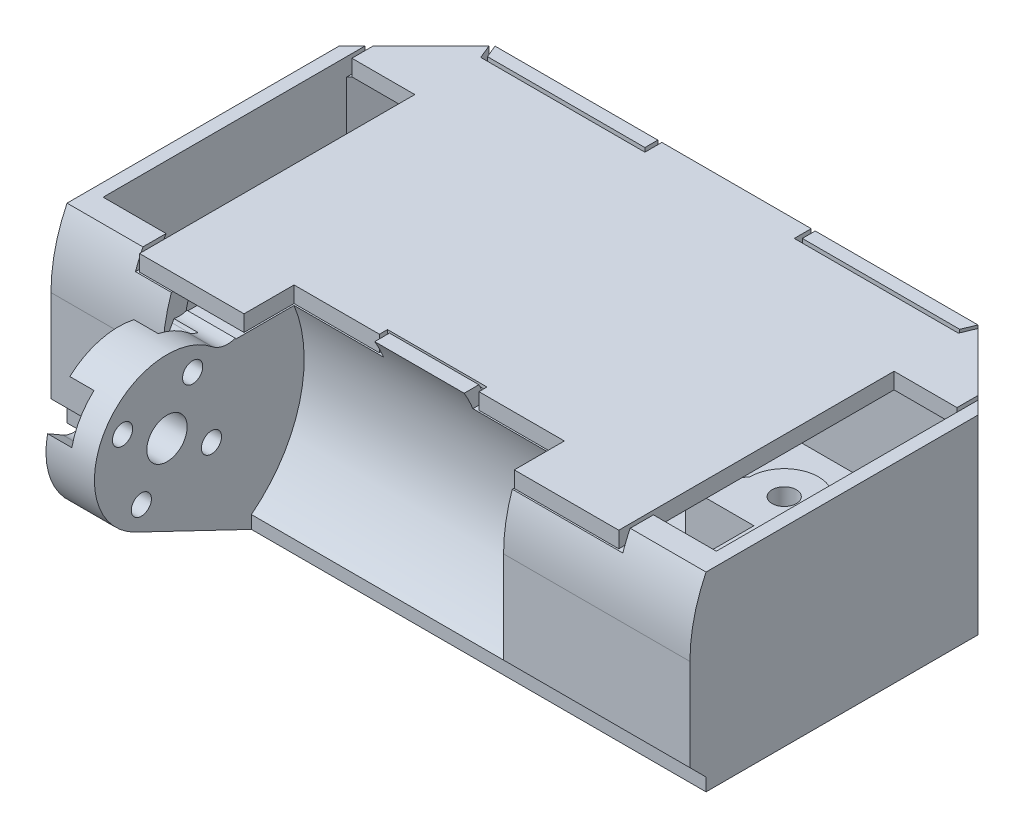
SolidWorks part; units mm, degrees
material "ABS PC"
ref_plane "Front Plane" through (0, 0, 0) normal (0, 0, 1) x (1, 0, 0)
ref_plane "Top Plane" through (0, 0, 0) normal (0, 1, 0) x (1, 0, 0)
ref_plane "Right Plane" through (0, 0, 0) normal (1, 0, 0) x (0, 0, -1)
sketch "Sketch1" plane through (0, 0, 0) normal (0, 1, 0) x (1, 0, 0)
  line L0 (0, -309.2525) -> (0, 15153.3717) construction
  line L1 (28.2, 1.5) -> (28.2, -1.5) construction
  line L2 (3, -6) -> (27, -6)
  line L3 (3, -6) -> (3, 6)
  line L4 (3, 6) -> (27, 6)
  line L5 (27, -6) -> (27, 6)
  line L6 (15, 6) -> (15, -6) construction
  line L7 (3, 0) -> (27, 0) construction
  line L8 (27.7, -2) -> (27, -2)
  line L9 (27.7, -2) -> (27.7, 2)
  line L10 (27.7, 2) -> (27, 2)
  line L11 (27, -2) -> (27, 2)
  line L12 (27.35, 2) -> (27.35, -2) construction
  line L13 (27.7, 0) -> (27, 0) construction
  line L14 (37, -1.5) -> (27.7, -1.5)
  line L15 (37, -1.5) -> (37, 1.5)
  line L16 (37, 1.5) -> (27.7, 1.5)
  line L17 (27.7, -1.5) -> (27.7, 1.5)
  line L18 (32.35, 1.5) -> (32.35, -1.5) construction
  line L19 (37, 0) -> (27.7, 0) construction
  line L20 (36.8, -16) -> (30.2, -16)
  line L21 (36.8, -16) -> (36.8, 16)
  line L22 (36.8, 16) -> (30.2, 16)
  line L23 (30.2, -16) -> (30.2, 16)
  line L24 (33.5, 16) -> (33.5, -16) construction
  line L25 (36.8, 0) -> (30.2, 0) construction
  line L26 (27, -7.5) -> (15.5, -7.5)
  line L27 (27, -7.5) -> (27, 7.5)
  line L28 (27, 7.5) -> (15.5, 7.5)
  line L29 (15.5, -7.5) -> (15.5, 7.5)
  line L30 (21.25, 7.5) -> (21.25, -7.5) construction
  line L31 (27, 0) -> (3, 0) construction
  line L32 (-27, 0) -> (-3, 0) construction
  line L33 (-21.25, 7.5) -> (-21.25, -7.5) construction
  line L34 (-36.8, 0) -> (-30.2, 0) construction
  line L35 (-33.5, 16) -> (-33.5, -16) construction
  line L36 (-37, 0) -> (-27.7, 0) construction
  line L37 (-32.35, 1.5) -> (-32.35, -1.5) construction
  line L38 (-27.7, 0) -> (-27, 0) construction
  line L39 (-27.35, 2) -> (-27.35, -2) construction
  line L40 (-3, 0) -> (-27, 0) construction
  line L41 (-15, 6) -> (-15, -6) construction
  line L42 (-28.2, 1.5) -> (-28.2, -1.5) construction
  line L43 (-15.5, -7.5) -> (-15.5, 7.5)
  line L44 (-27, 7.5) -> (-15.5, 7.5)
  line L45 (-27, -7.5) -> (-27, 7.5)
  line L46 (-27, -7.5) -> (-15.5, -7.5)
  line L47 (-30.2, -16) -> (-30.2, 16)
  line L48 (-36.8, 16) -> (-30.2, 16)
  line L49 (-36.8, -16) -> (-36.8, 16)
  line L50 (-36.8, -16) -> (-30.2, -16)
  line L51 (-27.7, -1.5) -> (-27.7, 1.5)
  line L52 (-37, 1.5) -> (-27.7, 1.5)
  line L53 (-37, -1.5) -> (-37, 1.5)
  line L54 (-37, -1.5) -> (-27.7, -1.5)
  line L55 (-27, -2) -> (-27, 2)
  line L56 (-27.7, 2) -> (-27, 2)
  line L57 (-27.7, -2) -> (-27.7, 2)
  line L58 (-27.7, -2) -> (-27, -2)
  line L59 (-27, -6) -> (-27, 6)
  line L60 (-3, 6) -> (-27, 6)
  line L61 (-3, -6) -> (-3, 6)
  line L62 (-3, -6) -> (-27, -6)
  line L63 (38, -995.0782) -> (38, 49004.9218) construction
  line L64 (-38, -995.0782) -> (-38, 49004.9218) construction
  line L65 (22.75, -9) -> (22.75, 9) construction
  line L66 (18.5, -9) -> (18.5, 9)
  line L67 (27, -9) -> (27, 9)
  line L68 (-22.75, -9) -> (-22.75, 9) construction
  line L69 (-18.5, -9) -> (-18.5, 9)
  line L70 (-27, -9) -> (-27, 9)
  circle A0 centre (22.75, 9) radius 1.5
  circle A1 centre (22.75, -9) radius 1.5
  circle A2 centre (-22.75, -9) radius 1.5
  circle A3 centre (-22.75, 9) radius 1.5
  arc A4 (18.5, -9) -> (27, -9) centre (22.75, -9) ccw
  arc A5 (27, 9) -> (18.5, 9) centre (22.75, 9) ccw
  arc A6 (-18.5, -9) -> (-27, -9) centre (-22.75, -9) cw
  arc A7 (-27, 9) -> (-18.5, 9) centre (-22.75, 9) cw
  point P1 (15, 0)
  point P7 (27.35, 0)
  point P12 (32.35, 0)
  point P16 (21.25, 0)
  point P17 (33.5, 0)
  point P77 (-33.5, 0)
  point P78 (-21.25, 0)
  point P79 (-32.35, 0)
  point P85 (-27.35, 0)
  point P86 (-15, 0)
  point P88 (38, 0)
  point P90 (22.75, 0)
  point P95 (-22.75, 0)
  point P100 (22.75, -13.25)
  point P104 (22.75, 13.25)
  point P107 (-22.75, 13.25)
  point P108 (-22.75, -13.25)
  dimension "D12" = 3
  dimension "D1" = 3
  dimension "D2" = 12
  dimension "D3" = 24
  dimension "D4" = 0.7
  dimension "D5" = 4
  dimension "D6" = 3
  dimension "D7" = 10
  dimension "D8" = 11.5
  dimension "D9" = 15
  dimension "D10" = 18
  dimension "D13" = 6.6
  dimension "D14" = 32
  dimension "D15" = 0.5
  dimension "D16" = 8.6
  dimension "D11" = 4.25
  dimension "D17" = 1
  dimension "D18" = 76
  dimension "D19" = 8.5
  dimension "D20" = 31
sketch "Sketch2" plane through (0, 0, 0) normal (0, 0, 1) x (1, 0, 0)
  line L0 (36.8, 0) -> (30.2, 0) construction
  line L1 (30.2, 32) -> (36.8, 32)
  line L2 (30.2, 32) -> (30.2, 0)
  line L3 (30.2, 0) -> (36.8, 0)
  line L4 (36.8, 32) -> (36.8, 0)
  line L5 (33.5, 0) -> (33.5, 32) construction
  line L6 (30.2, 16) -> (36.8, 16) construction
  line L7 (0, -1000) -> (0, 49000) construction
  line L8 (3, 0) -> (27, 0) construction
  line L9 (3, 11) -> (27, 11)
  line L10 (3, 11) -> (3, 21)
  line L11 (3, 21) -> (27, 21)
  line L12 (27, 11) -> (27, 21)
  line L13 (15, 21) -> (15, 11) construction
  line L14 (3, 16) -> (27, 16) construction
  line L15 (38, -960.9891) -> (38, 49039.0109) construction
  line L16 (15.5, 22.5) -> (27, 22.5)
  line L17 (15.5, 22.5) -> (15.5, 11)
  line L18 (15.5, 11) -> (27, 11)
  line L19 (27, 22.5) -> (27, 11)
  line L20 (21.25, 11) -> (21.25, 22.5) construction
  line L21 (15.5, 16.75) -> (27, 16.75) construction
  line L22 (-15.5, 16.75) -> (-27, 16.75) construction
  line L23 (-21.25, 11) -> (-21.25, 22.5) construction
  line L24 (-3, 16) -> (-27, 16) construction
  line L25 (-15, 21) -> (-15, 11) construction
  line L26 (-30.2, 16) -> (-36.8, 16) construction
  line L27 (-33.5, 0) -> (-33.5, 32) construction
  line L28 (-27, 22.5) -> (-27, 11)
  line L29 (-15.5, 11) -> (-27, 11)
  line L30 (-15.5, 22.5) -> (-15.5, 11)
  line L31 (-15.5, 22.5) -> (-27, 22.5)
  line L32 (-27, 11) -> (-27, 21)
  line L33 (-3, 21) -> (-27, 21)
  line L34 (-3, 11) -> (-3, 21)
  line L35 (-3, 11) -> (-27, 11)
  line L36 (-36.8, 32) -> (-36.8, 0)
  line L37 (-30.2, 0) -> (-36.8, 0)
  line L38 (-30.2, 32) -> (-30.2, 0)
  line L39 (-30.2, 32) -> (-36.8, 32)
  line L40 (-38, -960.9891) -> (-38, 49039.0109) construction
  point P0 (33.5, 16)
  point P4 (15, 16)
  point P12 (21.25, 16.75)
  point P42 (-21.25, 16.75)
  point P43 (-15, 16)
  point P44 (-33.5, 16)
  dimension "D1" = 32
  dimension "D2" = 10
  dimension "D3" = 11.5
sketch "Sketch3" plane through (0, 0, 0) normal (1, 0, 0) x (0, 0, -1)
  line L0 (34.1, 0) -> (-34.1, 0) construction
  line L1 (-1063.3991, 0) -> (48936.6009, 0) construction
  line L2 (-1069.8118, 11) -> (48930.1882, 11) construction
  line L4 (-1068.0845, 1) -> (48931.9155, 1) construction
  line L6 (-1000, 16) -> (49000, 16) construction
  line L7 (-1068.0845, 24.6) -> (48931.9155, 24.6) construction
  line L8 (-1063.3991, 32) -> (48936.6009, 32) construction
  line L9 (0, -984) -> (0, 49016) construction
  line L10 (-1013.3999, 22.6) -> (48986.6001, 22.6) construction
  line L11 (-1059.4795, 2.6) -> (48940.5205, 2.6) construction
  circle A0 centre (0, 16) radius 16
  circle A1 centre (-28, 16) radius 16
  circle A2 centre (-28, 16) radius 7
  circle A3 centre (-28, 16) radius 11.5
  circle A4 centre (-28, 16) radius 17 construction
  circle A5 centre (0, 16) radius 17 construction
  point P9 (-12, 16)
  point P10 (-16, 16)
  point P20 (-14.6642, 24.6)
  point P22 (0, 1)
  point P29 (0, 24.6)
  point P32 (0, 32)
  point P34 (0, 22.6)
  point P37 (0, 2.6)
  point P39 (-15.6665, 22.6)
  point P40 (-21, 16)
  point P41 (-16.5, 16)
  point P42 (14.6642, 24.6)
  point P46 (-17.5386, 2.6)
  point P47 (15.6665, 22.6)
  dimension "D1" = 14
  dimension "D3" = 23
  dimension "D2" = 6
  dimension "D4" = 2
  dimension "D5" = 1.6
  dimension "D6" = 20
  dimension "D7" = 20
  dimension "D9" = 1
  dimension "D8" = 1
  dimension "D10" = 1
ref_plane "Plane1" through (0, 11, 0) normal (0, 1, 0) x (1, 0, 0)
ref_plane "Plane2" through (0, 1, 0) normal (0, 1, 0) x (1, 0, 0)
sketch "Sketch4" plane through (0, 1, 0) normal (0, 1, 0) x (1, 0, 0)
  line L0 (-38, -200995.0782) -> (-38, 249004.9218) construction
  line L1 (39.6, 25.8404) -> (-39.6, 25.8404)
  line L2 (39.6, 25.8404) -> (39.6, -17.5386)
  line L3 (39.6, -17.5386) -> (-39.6, -17.5386)
  line L4 (-39.6, 25.8404) -> (-39.6, -17.5386)
  line L5 (0, -17.5386) -> (0, 25.8404) construction
  line L6 (39.6, 4.1509) -> (-39.6, 4.1509) construction
  line L7 (-38, 24.2404) -> (-39.6, 24.2404) construction
  line L8 (38, 24.2404) -> (-38, 24.2404) construction
  line L9 (38, 24.2404) -> (38, -17.5386) construction
  line L10 (38, -17.5386) -> (-38, -17.5386) construction
  line L11 (-38, 24.2404) -> (-38, -17.5386) construction
  line L12 (0, -17.5386) -> (0, 24.2404) construction
  line L13 (38, 3.3509) -> (-38, 3.3509) construction
  line L14 (-38, 24.2404) -> (-38, 25.8404) construction
  line L18 (-20, 22.2404) -> (20, 22.2404) construction
  line L19 (-20, 22.2404) -> (-20, 12.2404) construction
  line L20 (-20, 12.2404) -> (20, 12.2404) construction
  line L21 (20, 22.2404) -> (20, 12.2404) construction
  line L22 (0, 12.2404) -> (0, 22.2404) construction
  line L23 (-20, 17.2404) -> (20, 17.2404) construction
  arc A0 (27, 9) -> (18.5, 9) centre (22.75, 9) ccw construction
  point P0 (0, 4.1509)
  point P4 (0, 17.2404)
  point P8 (0, 3.3509)
  dimension "D1" = 1.6
  dimension "D2" = 10
  dimension "D3" = 40
  dimension "D4" = 2
extrude "Boss-Extrude1" add sketch "Sketch4" along normal up to vertex (1.6 mm away) up to point (0, 2.6, 0)
sketch "Sketch5" plane through (0, 2.6, 0) normal (0, 1, 0) x (1, 0, 0)
  line L5 (27, -9) -> (27, 9) construction
  line L6 (27, -9) -> (27, 9)
  line L7 (0, -1000) -> (0, 49000) construction
  line L8 (18.5, 9) -> (17.375, 7.5)
  line L9 (27, 7.5) -> (15.5, 7.5) construction
  line L14 (17.375, 7.5) -> (15.5, 7.5)
  line L15 (15.5, 7.5) -> (15.5, -7.5)
  line L16 (15.5, -7.5) -> (17.375, -7.5)
  line L17 (27, -7.5) -> (15.5, -7.5) construction
  line L18 (17.375, -7.5) -> (18.5, -9)
  line L19 (-15.5, -7.5) -> (-17.375, -7.5)
  line L20 (-15.5, 7.5) -> (-15.5, -7.5)
  line L21 (-17.375, 7.5) -> (-15.5, 7.5)
  line L22 (-18.5, 9) -> (-17.375, 7.5)
  line L23 (-27, -9) -> (-27, 9)
  line L24 (-17.375, -7.5) -> (-18.5, -9)
  arc A3 (27, 9) -> (18.5, 9) centre (22.75, 9) ccw construction
  arc A4 (27, 9) -> (18.5, 9) centre (22.75, 9) ccw
  arc A5 (18.5, -9) -> (27, -9) centre (22.75, -9) ccw construction
  arc A6 (18.5, -9) -> (27, -9) centre (22.75, -9) ccw
  arc A7 (-27, 9) -> (-18.5, 9) centre (-22.75, 9) cw
  arc A8 (-18.5, -9) -> (-27, -9) centre (-22.75, -9) cw
extrude "Boss-Extrude2" add sketch "Sketch5" along normal up to surface (8.4 mm away) up to plane "Plane1"
sketch "Sketch15" plane through (0, 11, 0) normal (0, 1, 0) x (1, 0, 0)
  line L0 (-27, -7.5) -> (-27, 7.5) construction
  line L1 (24, -4) -> (-24, -4)
  line L2 (24, -4) -> (24, 4)
  line L3 (24, 4) -> (-24, 4)
  line L4 (-24, -4) -> (-24, 4)
  line L5 (0, 4) -> (0, -4) construction
  line L6 (24, 0) -> (-24, 0) construction
  line L7 (-3, -6) -> (-27, -6) construction
  point P0 (0, 0)
  dimension "D1" = 3
  dimension "D2" = 2
extrude "Cut-Extrude2" cut sketch "Sketch15" against normal up to surface (8.4 mm away) up to face at (19.5938, 2.6, 0)
sketch "Sketch6" plane through (0, 2.6, 0) normal (0, 1, 0) x (1, 0, 0)
  line L0 (0, -1000) -> (0, 49000) construction
  line L1 (38, -200995.0782) -> (38, 249004.9218) construction
  line L2 (29, -16) -> (38, -16)
  line L3 (29, -16) -> (29, 16)
  line L4 (29, 16) -> (38, 16)
  line L5 (38, -16) -> (38, 16)
  line L6 (33.5, 16) -> (33.5, -16) construction
  line L7 (29, 0) -> (38, 0) construction
  line L8 (36.8, 16) -> (30.2, 16) construction
  line L9 (-29, 0) -> (-38, 0) construction
  line L10 (-33.5, 16) -> (-33.5, -16) construction
  line L11 (-38, -16) -> (-38, 16)
  line L12 (-29, 16) -> (-38, 16)
  line L13 (-29, -16) -> (-29, 16)
  line L14 (-29, -16) -> (-38, -16)
  point P1 (33.5, 0)
  point P22 (-33.5, 0)
extrude "Cut-Extrude1" cut sketch "Sketch6" against normal through all
sketch "Sketch8" plane through (38, 0, 0) normal (-1, 0, 0) x (0, 0, 1)
  line L0 (10.6416, 2.6) -> (9.0416, 1)
  line L1 (9.0416, 1) -> (16, 1)
  line L2 (16, 1) -> (16, 2.6)
  line L3 (16, 2.6) -> (10.6416, 2.6)
  line L4 (0, -1000) -> (0, 49000) construction
  line L5 (-16, 2.6) -> (-10.6416, 2.6)
  line L6 (-16, 1) -> (-16, 2.6)
  line L7 (-9.0416, 1) -> (-16, 1)
  line L8 (-10.6416, 2.6) -> (-9.0416, 1)
  circle A1 centre (0, 16) radius 17 construction
  dimension "D1" = 45
extrude "Boss-Extrude3" add sketch "Sketch8" along normal up to surface (76 mm away) up to face at (-38, 1.8, 0)
ref_plane "Plane3" through (0, 32, 0) normal (0, 1, 0) x (1, 0, 0)
ref_plane "Plane4" through (0, 24.6, 0) normal (0, 1, 0) x (1, 0, 0)
sketch "Sketch10" plane through (0, 2.6, 0) normal (0, 1, 0) x (1, 0, 0)
  line L0 (-38, 24.2404) -> (-38, -17.5386)
  line L1 (-38, -17.5386) -> (-39.6, -17.5386)
  line L2 (-39.6, -17.5386) -> (-39.6, 25.8404)
  line L3 (-39.6, 25.8404) -> (39.6, 25.8404)
  line L4 (39.6, 25.8404) -> (39.6, -17.5386)
  line L5 (39.6, -17.5386) -> (38, -17.5386)
  line L6 (38, -17.5386) -> (38, 24.2404)
  line L7 (38, 24.2404) -> (-38, 24.2404)
extrude "Boss-Extrude4" add sketch "Sketch10" along normal up to vertex (22 mm away) up to point (0, 24.6, 0)
ref_plane "Plane6" through (-22.75, 0, 0) normal (1, 0, 0) x (0, 0, -1)
sketch "Sketch11" plane through (-22.75, 0, 0) normal (1, 0, 0) x (0, 0, -1)
  line L0 (-9, 11) -> (-13.25, 11)
  line L1 (-9, 11) -> (-9, 1)
  line L2 (-9, 1) -> (-17.5386, 1)
  line L4 (4, 11) -> (-4, 11) construction
  line L5 (-201000, 16) -> (249000, 16) construction
  line L6 (-17.5386, 1) -> (-31.8925, 7.8853)
  line L7 (-13.25, 11) -> (-20.7164, 21.2867)
  arc A0 (-20.7164, 21.2867) -> (-31.8925, 7.8853) centre (-28, 16) ccw
  circle A2 centre (-28, 16) radius 7 construction
  point P7 (-37, 16)
  point P13 (-35, 16)
  dimension "D2" = 2
extrude "Boss-Extrude5" add sketch "Sketch11" along normal blind 4
sketch "Sketch12" plane through (-38, 0, 0) normal (1, 0, 0) x (0, 0, -1)
  line L5 (-17.5386, 24.6) -> (24.2404, 24.6) construction
  line L6 (-17, 16) -> (-17, 2.6)
  line L7 (-17.5386, 2.6) -> (-10.6416, 2.6) construction
  line L8 (-17, 2.6) -> (-17.5386, 2.6)
  line L9 (-17.5386, 2.6) -> (-19.5337, 4.595)
  line L10 (-19.5337, 4.595) -> (-19.5337, 16)
  line L11 (-14.6642, 24.6) -> (-17.5386, 24.6)
  arc A2 (-14.6642, 24.6) -> (-17, 16) centre (0, 16) ccw
  circle A3 centre (0, 16) radius 17
  circle A4 centre (0, 16) radius 17 construction
  arc A5 (-17.5386, 24.6) -> (-19.5337, 16) centre (0, 16) ccw
  dimension "D1" = 1
  dimension "D2" = 45
extrude "Boss-Extrude6" add sketch "Sketch12" along normal up to surface and the other way up to surface up to face at (-18.75, 9.2215, 18.6308) other way up to face at (-39.6, 12.8, -4.1509)
sketch "Sketch13" plane through (-18.75, 0, 0) normal (1, 0, 0) x (0, 0, -1)
  line L2 (-14.6642, 24.6) -> (24.2404, 24.6) construction
  line L5 (-10.4361, 2.6) -> (-17.5386, 2.6) construction
  line L6 (-13.3358, 24.6) -> (-11.5076, 24.6)
  line L7 (-15.1004, 2.6) -> (-17.5386, 2.6)
  arc A0 (-13.3358, 24.6) -> (-17.5386, 2.6) centre (-28, 16) cw
  arc A1 (-11.5076, 24.6) -> (-15.1004, 2.6) centre (-28, 16) cw
  arc A2 (-12.9263, 23.8602) -> (-16.21, 3.7527) centre (-28, 16) cw construction
  circle A3 centre (-28, 16) radius 17 construction
  dimension "D1" = 1.6
extrude "Boss-Extrude7" add sketch "Sketch13" along normal up to vertex (37.25 mm away) up to point (18.5, 0, 9)
sketch "Sketch14" plane through (-18.75, 0, 0) normal (1, 0, 0) x (0, 0, -1)
  line L0 (-13.3358, 24.6) -> (-14.6642, 24.6)
  line L8 (-17.5386, 1) -> (-17.5386, 2.6)
  line L9 (-11.7519, 11) -> (-13.25, 11)
  line L10 (-13.25, 11) -> (-16.9992, 16.1654)
  line L13 (-14.6642, 24.6) -> (-17.5386, 24.6)
  line L14 (-19.257, 19.276) -> (-20.7164, 21.2867)
  line L15 (-31.8925, 7.8853) -> (-17.5386, 1)
  line L16 (-17.5386, 1) -> (-17.5386, 2.6)
  line L22 (-19.257, 19.276) -> (-20.7164, 21.2867)
  line L23 (-31.8925, 7.8853) -> (-17.5386, 1)
  line L24 (-14.6642, 24.6) -> (-17.5386, 24.6)
  arc A2 (-17.5386, 2.6) -> (-11.7519, 11) centre (-28, 16) ccw
  arc A3 (-20.7164, 21.2867) -> (-31.8925, 7.8853) centre (-28, 16) ccw
  arc A5 (-20.7164, 21.2867) -> (-31.8925, 7.8853) centre (-28, 16) ccw
  arc A6 (-13.3358, 24.6) -> (-17.5386, 2.6) centre (-28, 16) cw
  circle A7 centre (-28, 16) radius 16 construction
  arc A12 (-14.6642, 24.6) -> (-16.9992, 16.1654) centre (0, 16) ccw
  arc A14 (-17.5386, 24.6) -> (-19.257, 19.276) centre (0, 16) ccw
  arc A15 (-17.5386, 24.6) -> (-19.257, 19.276) centre (0, 16) ccw
  dimension "D1" = 0
extrude "Boss-Extrude8" add sketch "Sketch14" along normal blind 2
sketch "Sketch19" plane through (38, 0, 0) normal (-1, 0, 0) x (0, 0, 1)
  line L5 (19.5337, 4.595) -> (19.5337, 16)
  line L6 (17.5386, 2.6) -> (19.5337, 4.595)
  line L7 (17, 2.6) -> (17.5386, 2.6)
  line L8 (17, 16) -> (17, 2.6)
  line L9 (17.5386, 24.6) -> (14.6642, 24.6)
  line L10 (19.5337, 4.595) -> (19.5337, 16)
  line L11 (17.5386, 2.6) -> (19.5337, 4.595)
  line L12 (17, 2.6) -> (17.5386, 2.6)
  line L13 (17, 16) -> (17, 2.6)
  line L14 (17.5386, 24.6) -> (14.6642, 24.6)
  arc A2 (17, 16) -> (14.6642, 24.6) centre (0, 16) ccw
  arc A3 (19.5337, 16) -> (17.5386, 24.6) centre (0, 16) ccw
  arc A4 (17, 16) -> (14.6642, 24.6) centre (0, 16) ccw
  arc A5 (19.5337, 16) -> (17.5386, 24.6) centre (0, 16) ccw
  dimension "D1" = 0
extrude "Boss-Extrude10" add sketch "Sketch19" along normal up to surface (19.5 mm away) and the other way up to surface (1.6 mm away) up to face at (18.5, 13.253, 12.4216) other way up to face at (39.6, 12.8, -4.1509)
sketch "Sketch20" plane through (18.5, 0, 0) normal (-1, 0, 0) x (0, 0, 1)
  line L0 (17.5386, 24.6) -> (14.6642, 24.6) construction
  line L1 (19.5337, 4.595) -> (19.5337, 16) construction
  line L2 (17.5386, 24.6) -> (14.6642, 24.6)
  line L3 (19.5337, 4.595) -> (19.5337, 16)
  line L4 (17.5386, 2.6) -> (19.5337, 4.595) construction
  line L5 (17.5386, 2.6) -> (19.5337, 4.595)
  line L7 (14.6642, 24.6) -> (13.3358, 24.6)
  arc A1 (19.5337, 16) -> (17.5386, 24.6) centre (0, 16) ccw construction
  arc A3 (19.5337, 16) -> (17.5386, 24.6) centre (0, 16) ccw
  arc A4 (13.3358, 24.6) -> (17.5386, 2.6) centre (28, 16) ccw
  circle A5 centre (28, 16) radius 16 construction
extrude "Boss-Extrude13" add sketch "Sketch20" along normal blind 2
fillet "Fillet1" radius 3 1 edges at (-19.75, 19.276, 19.257)
sketch "Sketch16" plane through (0, 2.6, 0) normal (0, 1, 0) x (1, 0, 0)
  line L0 (-39.6, 16.1698) -> (-29.9295, 25.8404)
  line L1 (-29.9295, 25.8404) -> (-27.6667, 25.8404)
  line L2 (-27.6667, 25.8404) -> (-39.6, 13.9071)
  line L3 (-39.6, 13.9071) -> (-39.6, 16.1698)
  line L4 (-34.7647, 21.0051) -> (-33.6334, 19.8737) construction
  line L5 (39.6, 25.8404) -> (-39.6, 25.8404) construction
  line L6 (-39.6, 25.8404) -> (-39.6, -17.5386) construction
  line L7 (-38, 24.2404) -> (-38, 25.8404) construction
  line L8 (0, -946.4498) -> (0, 47696.3752) construction
  line L10 (27.6667, 25.8404) -> (39.6, 13.9071)
  line L11 (29.9295, 25.8404) -> (27.6667, 25.8404)
  line L12 (39.6, 16.1698) -> (29.9295, 25.8404)
  line L13 (39.6, 13.9071) -> (39.6, 16.1698)
  dimension "D1" = 0.5
extrude "Boss-Extrude9" add sketch "Sketch16" along normal up to surface (22 mm away) up to face at (-0.0625, 24.6, 5.6432)
sketch "Sketch17" plane through (0, 1, 0) normal (0, -1, 0) x (1, 0, 0)
  line L0 (39.6, -16.1698) -> (29.9295, -25.8404) construction
  line L1 (-39.6, -16.1698) -> (-29.9295, -25.8404) construction
  line L2 (39.6, -16.1698) -> (29.9295, -25.8404)
  line L3 (-39.6, -16.1698) -> (-29.9295, -25.8404)
  line L4 (-39.6, -16.1698) -> (-39.6, -25.8404)
  line L5 (-39.6, -25.8404) -> (-29.9295, -25.8404)
  line L6 (29.9295, -25.8404) -> (39.6, -25.8404)
  line L7 (39.6, -25.8404) -> (39.6, -16.1698)
extrude "Cut-Extrude3" cut sketch "Sketch17" against normal through all
sketch "Sketch18" plane through (0, 1, 0) normal (0, -1, 0) x (1, 0, 0)
  circle A0 centre (-22.75, -9) radius 1.5
  circle A1 centre (-22.75, 9) radius 1.5
  circle A2 centre (22.75, 9) radius 1.5
  circle A3 centre (22.75, -9) radius 1.5
  circle A4 centre (22.75, -9) radius 1.5 construction
  circle A5 centre (22.75, 9) radius 1.5 construction
  circle A6 centre (-22.75, 9) radius 1.5 construction
  circle A7 centre (-22.75, -9) radius 1.5 construction
  dimension "D1" = 3
extrude "Cut-Extrude4" cut sketch "Sketch18" against normal through all
chamfer "Chamfer1" distance 2 angle 45 4 edges at (-22.75, 1, 7.5) (-22.75, 1, -10.5) (22.75, 1, -10.5) (22.75, 1, 7.5)
sketch "Sketch21" plane through (0, 24.6, 0) normal (0, 1, 0) x (1, 0, 0)
  line L0 (-30.2, -16) -> (-30.2, 16) construction
  line L1 (-30.2, -19.5337) -> (-16.75, -19.5337)
  line L2 (-16.75, -19.5337) -> (-5.6667, -19.5337)
  line L4 (-30.2, -19.5337) -> (-30.2, 15.6665)
  line L5 (-30.2, 15.6665) -> (-38, 15.6665)
  line L7 (0, -999.5952) -> (0, 48990.2839) construction
  line L8 (5.4167, -19.5337) -> (16.5, -19.5337)
  line L9 (16.5, -19.5337) -> (30.2, -19.5337)
  line L10 (-38, 15.6665) -> (-38, 17.7698)
  line L11 (-38, 17.7698) -> (-29.9295, 25.8404)
  line L12 (-29.9295, 25.8404) -> (-29.2667, 24.2404)
  line L13 (38, 24.2404) -> (-38, 24.2404) construction
  line L14 (-27.6667, 25.8404) -> (-39.6, 13.9071) construction
  line L15 (29.9295, 25.8404) -> (29.2667, 24.2404)
  line L16 (38, 17.7698) -> (29.9295, 25.8404)
  line L17 (38, 15.6665) -> (38, 17.7698)
  line L18 (30.2, 15.6665) -> (38, 15.6665)
  line L19 (30.2, -19.5337) -> (30.2, 15.6665)
  line L21 (-29.2667, 24.2404) -> (-9.7556, 24.2404)
  line L22 (-9.7556, 24.2404) -> (-9.7556, 25.8404)
  line L23 (-9.7556, 25.8404) -> (9.7556, 25.8404)
  line L24 (9.7556, 25.8404) -> (9.7556, 24.2404)
  line L25 (9.7556, 24.2404) -> (29.2667, 24.2404)
  line L26 (39.6, 25.8404) -> (-39.6, 25.8404) construction
  line L27 (-38, -200995.0782) -> (-38, 249004.9218) construction
  line L28 (-39.6, 16.1698) -> (-29.9295, 25.8404) construction
  line L29 (-16.75, -37) -> (-16.75, -22.3719) construction
  line L30 (16.5, -17.5386) -> (16.5, -13.3358) construction
  line L31 (-22.75, -19.5337) -> (-39.6, -19.5337) construction
  line L32 (-5.6667, -19.5337) -> (-5.6667, -6)
  line L33 (-5.6667, -6) -> (5.4167, -6)
  line L34 (5.4167, -6) -> (5.4167, -19.5337)
extrude "Cut-Extrude5" cut sketch "Sketch21" against normal blind 2.2
sketch "Sketch26" plane through (0, 24.6, 0) normal (0, 1, 0) x (1, 0, 0)
  line L0 (-27.6667, 25.8404) -> (-39.6, 13.9071) construction
  line L1 (-38, 15.6665) -> (38, 15.6665)
  line L2 (-38, 15.6665) -> (-38, 15.5071)
  line L3 (-38, 15.5071) -> (38, 15.5071)
  line L4 (38, 15.6665) -> (38, 15.5071)
  line L5 (27.6667, 25.8404) -> (39.6, 13.9071) construction
extrude "Cut-Extrude10" cut sketch "Sketch26" against normal up to surface (2.2 mm away) up to face at (-34.6074, 22.4, -19.8367)
sketch "Sketch22" plane through (0, 24.6, 0) normal (0, 1, 0) x (1, 0, 0)
  line L0 (-37.5, -14.1642) -> (-29.7, -14.1642)
  line L1 (-35.1854, -14.1642) -> (-35.1854, -14.6642) construction
  line L2 (-37.5, -14.1642) -> (-38, -14.1642) construction
  line L3 (-38, -200995.0782) -> (-38, 249004.9218) construction
  line L4 (-37.5, -14.1642) -> (-37.5, 18.2698)
  line L5 (-37.5, 18.2698) -> (-30.3122, 25.4577)
  line L6 (-39.6, 16.1698) -> (-29.9295, 25.8404) construction
  line L7 (-30.3122, 25.4577) -> (-29.6008, 23.7404)
  line L8 (-29.6008, 23.7404) -> (-9.2556, 23.7404)
  line L9 (-29.9295, 25.8404) -> (-29.2667, 24.2404) construction
  line L10 (-29.2667, 24.2404) -> (-29.7287, 24.049) construction
  line L11 (-19.4282, 23.7404) -> (-19.4282, 24.2404) construction
  line L12 (-29.2667, 24.2404) -> (-9.7556, 24.2404) construction
  line L13 (-9.2556, 23.7404) -> (-9.2556, 25.8404)
  line L14 (39.6, 25.8404) -> (-39.6, 25.8404) construction
  line L15 (-9.7556, 24.2404) -> (-9.2556, 24.2404) construction
  line L16 (-29.7, -14.1642) -> (-29.7, -18.4555)
  line L17 (-30.2, -18.4555) -> (-22.75, -18.4555) construction
  line L18 (-29.7, -18.4555) -> (-30.2, -18.4555) construction
  line L19 (-30.2, -19.5337) -> (-30.2, 15.6665) construction
  line L20 (-29.7, -18.4555) -> (-16.75, -18.4555)
  line L21 (-16.75, -18.4555) -> (-16.75, -12.2507)
  line L22 (-16.75, -12.2507) -> (-5.6667, -12.2507) construction
  line L23 (-16.75, -19.5337) -> (-16.75, -12.2507) construction
  line L24 (0, -1000) -> (0, 49000) construction
  line L25 (16.75, -18.4555) -> (16.75, -12.2507)
  line L26 (29.7, -18.4555) -> (16.75, -18.4555)
  line L27 (29.7, -14.1642) -> (29.7, -18.4555)
  line L28 (37.5, -14.1642) -> (29.7, -14.1642)
  line L29 (37.5, -14.1642) -> (37.5, 18.2698)
  line L30 (37.5, 18.2698) -> (30.3122, 25.4577)
  line L31 (30.3122, 25.4577) -> (29.6008, 23.7404)
  line L32 (29.6008, 23.7404) -> (9.2556, 23.7404)
  line L33 (9.2556, 23.7404) -> (9.2556, 25.8404)
  line L35 (-9.2556, 25.8404) -> (9.2556, 25.8404)
  line L36 (-16.75, -12.2507) -> (-6.1667, -12.2507)
  line L37 (-6.1667, -12.2507) -> (-6.1667, -11.2507)
  line L38 (-6.1667, -11.2507) -> (6.1667, -11.2507)
  line L39 (-6.1667, -11.7507) -> (-5.6667, -11.7507) construction
  line L40 (-5.6667, -19.5337) -> (-5.6667, -6) construction
  line L41 (16.75, -12.2507) -> (6.1667, -12.2507)
  line L42 (6.1667, -12.2507) -> (6.1667, -11.2507)
  point P64 (0, -11.2507)
  dimension "D1" = 0.5
  dimension "D2" = 1
extrude "Boss-Extrude14" add sketch "Sketch22" against normal blind 2 separate body
chamfer "Chamfer2" distance 1.6 angle 45 1 edges at (0, 22.6, 11.2507)
sketch "Sketch24" plane through (0, 24.6, 0) normal (0, 1, 0) x (1, 0, 0)
  line L1 (-29.7, -15.6665) -> (-37.5, -15.6665)
  line L2 (-29.7, -15.6665) -> (-29.7, 15.6665)
  line L3 (-29.7, 15.6665) -> (-37.5, 15.6665)
  line L4 (-37.5, -15.6665) -> (-37.5, 15.6665)
  line L5 (-33.6, 15.6665) -> (-33.6, -15.6665) construction
  line L6 (-29.7, 0) -> (-37.5, 0) construction
  line L8 (29.7, -15.6665) -> (37.5, -15.6665)
  line L9 (29.7, -15.6665) -> (29.7, 15.6665)
  line L10 (29.7, 15.6665) -> (37.5, 15.6665)
  line L11 (37.5, -15.6665) -> (37.5, 15.6665)
  line L12 (33.6, 15.6665) -> (33.6, -15.6665) construction
  line L13 (29.7, 0) -> (37.5, 0) construction
  line L14 (29.7, -14.1642) -> (29.7, -18.4555) construction
  line L15 (37.5, -14.1642) -> (37.5, 18.2698) construction
  line L16 (3, 0) -> (27, 0) construction
  line L17 (-37.5, -14.1642) -> (-37.5, 18.2698) construction
  line L18 (-27, 0) -> (-3, 0) construction
  point P0 (-33.6, 0)
  point P8 (33.6, 0)
extrude "Cut-Extrude8" cut sketch "Sketch24" against normal through all
sketch "Sketch25" plane through (0, 0, 19.5337) normal (0, 0, 1) x (1, 0, 0)
  line L0 (-25.75, 22.4) -> (-22.75, 22.4)
  line L1 (-22.75, 22.4) -> (-22.75, 16)
  line L2 (-22.75, 16) -> (-24.25, 16)
  line L3 (-25.75, 22.4) -> (-25.75, 17.5)
  line L4 (-24.25, 17.5) -> (-25.75, 17.5) construction
  line L5 (-22.75, 16) -> (-39.6, 16) construction
  line L6 (-30.2, 22.4) -> (-22.75, 22.4) construction
  line L7 (-22.75, 22.4) -> (-22.75, 16) construction
  arc A0 (-25.75, 17.5) -> (-24.25, 16) centre (-24.25, 17.5) ccw
  dimension "D1" = 3
extrude "Cut-Extrude9" cut sketch "Sketch25" against normal blind 10
sketch "Sketch27" plane through (-16.75, 0, 0) normal (1, 0, 0) x (0, 0, -1)
  line L0 (-33.5114, 19.182) -> (-31.182, 10.4886) construction
  line L1 (-33.5114, 19.182) -> (-24.818, 21.5114) construction
  line L2 (-31.182, 10.4886) -> (-22.4886, 12.818) construction
  line L3 (-24.818, 21.5114) -> (-22.4886, 12.818) construction
  line L4 (-26.8353, 11.6533) -> (-29.1647, 20.3467) construction
  line L5 (-32.3467, 14.8353) -> (-23.6533, 17.1647) construction
  line L6 (-201000, 16) -> (249000, 16) construction
  circle A0 centre (-24.818, 21.5114) radius 1.25
  circle A1 centre (-22.4886, 12.818) radius 1.25
  circle A2 centre (-31.182, 10.4886) radius 1.25
  circle A3 centre (-33.5114, 19.182) radius 1.25
  circle A4 centre (-28, 16) radius 2.5
  point P1 (-28, 16)
  dimension "D3" = 2.5
  dimension "D4" = 5
  dimension "D1" = 9
  dimension "D2" = 15
extrude "Cut-Extrude11" cut sketch "Sketch27" against normal through all
sketch "Sketch29" plane through (-22.75, 0, 0) normal (-1, 0, 0) x (0, 0, 1)
  line L0 (33.5114, 19.182) -> (35.4215, 20.2848) construction
  line L1 (32.1364, 21.5636) -> (34.0465, 22.6664)
  line L2 (34.8864, 16.8004) -> (36.7965, 17.9032)
  line L7 (24.818, 21.5114) -> (23.7152, 23.4215) construction
  line L8 (22.4364, 20.1364) -> (21.3336, 22.0465)
  line L9 (27.1996, 22.8864) -> (26.0968, 24.7965)
  line L10 (31.182, 10.4886) -> (32.2848, 8.5785) construction
  line L11 (33.5636, 11.8636) -> (34.6664, 9.9535)
  line L12 (28.8004, 9.1136) -> (29.9032, 7.2035)
  arc A0 (32.1364, 21.5636) -> (34.8864, 16.8004) centre (33.5114, 19.182) ccw
  arc A1 (36.7965, 17.9032) -> (34.0465, 22.6664) centre (35.4215, 20.2848) ccw
  arc A4 (22.4364, 20.1364) -> (27.1996, 22.8864) centre (24.818, 21.5114) ccw
  arc A5 (26.0968, 24.7965) -> (21.3336, 22.0465) centre (23.7152, 23.4215) ccw
  arc A6 (33.5636, 11.8636) -> (28.8004, 9.1136) centre (31.182, 10.4886) ccw
  arc A7 (29.9032, 7.2035) -> (34.6664, 9.9535) centre (32.2848, 8.5785) ccw
  arc A8 (31.8925, 7.8853) -> (20.7164, 21.2867) centre (28, 16) ccw construction
  circle A9 centre (22.4886, 12.818) radius 2.75
  circle A10 centre (22.4886, 12.818) radius 1.25 construction
  point P2 (34.4664, 19.7334)
  point P14 (24.2666, 22.4664)
  point P24 (31.7334, 9.5336)
  dimension "D1" = 5.5
extrude "Cut-Extrude12" cut sketch "Sketch29" against normal offset from surface (3 mm away) 3 up to face at (-16.75, 12.818, 21.2386)
equation "\"D1@Sketch2\"=\"D14@Sketch1\""
equation "\"D1@Boss-Extrude13\"=\"D1@Boss-Extrude8\""
